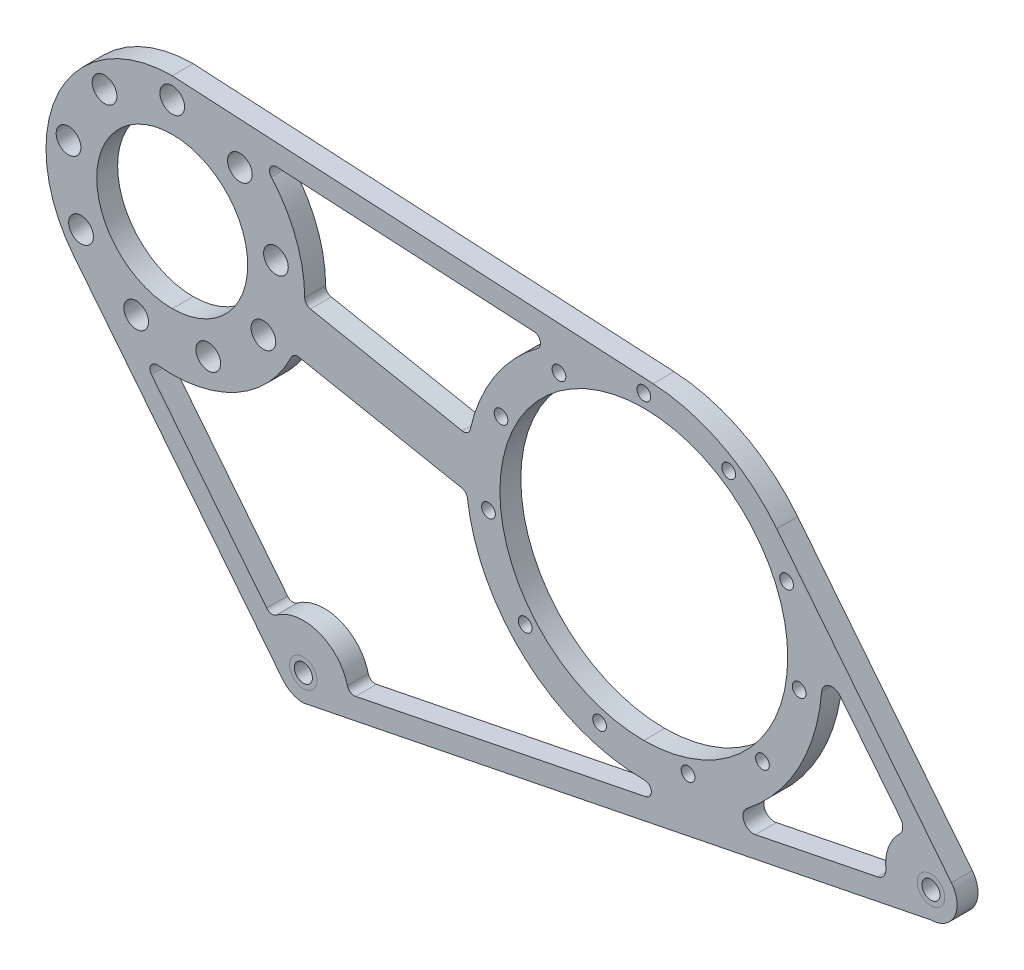
SolidWorks part; units mm, degrees
material "6061-T6 (SS)"
ref_plane "Front Plane" through (0, 0, 0) normal (0, 0, 1) x (1, 0, 0)
ref_plane "Top Plane" through (0, 0, 0) normal (0, 1, 0) x (1, 0, 0)
ref_plane "Right Plane" through (0, 0, 0) normal (1, 0, 0) x (0, 0, -1)
sketch "Sketch1" plane through (0, 0, 0) normal (0, 0, 1) x (1, 0, 0)
  line L0 (0, 0) -> (171.7726, -25.4) construction
  line L1 (47.761, -127.9853) -> (276.361, -82.1437)
  line L2 (0, 45.974) -> (175.1446, 36.4206)
  line L3 (-35.96, -28.6441) -> (40.3107, -124.3949)
  line L4 (220.1994, 13.1746) -> (283.8113, -66.6841)
  line L5 (171.7726, 36.5125) -> (171.7726, 27.0256) construction
  line L6 (0, 27.4955) -> (0, 45.974) construction
  circle A0 centre (0, 0) radius 45.974
  circle A1 centre (171.7726, -25.4) radius 61.9125
  circle A2 centre (171.7726, -25.4) radius 52.4256
  circle A3 centre (0, 0) radius 27.4955
  circle A4 centre (47.761, -118.4603) radius 9.525
  circle A5 centre (276.361, -72.6187) radius 9.525
  circle A6 centre (47.761, -118.4603) radius 3.2995
  circle A7 centre (276.361, -72.6187) radius 3.2995
  circle A19 centre (171.7726, -25.4) radius 57.1691 construction
  circle A21 centre (0, 0) radius 38.354 construction
  point P23 (0, 38.354)
  point P44 (0, 0)
  point P47 (171.7726, 31.7691)
  dimension "D1" = 91.948
  dimension "D2" = 123.825
  dimension "D5" = 104.8512
  dimension "D6" = 54.991
  dimension "D7" = 6.5989
  dimension "D8" = 6.5989
  dimension "D9" = 228.6
  dimension "D10" = 19.05
  dimension "D11" = 19.05
  dimension "D14" = 7.62
  dimension "D3" = 171.7726
  dimension "D4" = 25.4
  dimension "D12" = 117.2
  dimension "D13" = 76.2
extrude "Boss-Extrude1" add sketch "Sketch1" along normal blind 7.62 contours A5 L4 A1 L2 A0 L3 A4 L1 | L2 A0 A3 | A4 L1 A6 | A5 A7 | A1 A2 region at (43.7428, -126.7982, 0) region at (104.2025, -48.9688, 0) region at (268.0231, -68.6005, 0) region at (-40.2441, 19.3945, 0) region at (228.5635, -5.5459, 0)
sketch "Sketch2" plane through (0, 0, 7.62) normal (0, 0, 1) x (1, 0, 0)
  line L0 (171.7726, 36.5125) -> (171.7726, 27.0256) construction
  circle A0 centre (0, 38.354) radius 4.4996
  circle A1 centre (171.7726, 31.7691) radius 2.5006
  circle A2 centre (24.6535, 29.3809) radius 4.4996
  circle A3 centre (37.7713, 6.6601) radius 4.4996
  circle A4 centre (33.2155, -19.177) radius 4.4996
  circle A5 centre (13.1178, -36.041) radius 4.4996
  circle A6 centre (-13.1178, -36.041) radius 4.4996
  circle A7 centre (-33.2155, -19.177) radius 4.4996
  circle A8 centre (-37.7713, 6.6601) radius 4.4996
  circle A9 centre (-24.6535, 29.3809) radius 4.4996
  circle A10 centre (0, 0) radius 38.354 construction
  circle A11 centre (202.6805, 22.6937) radius 2.5006
  circle A12 centre (223.7754, -1.6511) radius 2.5006
  circle A13 centre (228.3597, -33.536) radius 2.5006
  circle A14 centre (214.9781, -62.8378) radius 2.5006
  circle A15 centre (187.879, -80.2533) radius 2.5006
  circle A16 centre (155.6662, -80.2533) radius 2.5006
  circle A17 centre (128.5671, -62.8378) radius 2.5006
  circle A18 centre (115.1854, -33.536) radius 2.5006
  circle A19 centre (119.7698, -1.6511) radius 2.5006
  circle A20 centre (140.8647, 22.6937) radius 2.5006
  circle A21 centre (171.7726, -25.4) radius 57.169 construction
  point P26 (0, 0)
  point P48 (171.7726, -25.4)
  dimension "D1" = 8.9992
  dimension "D2" = 5.0013
  dimension "D3" = 9
extrude "Cut-Extrude1" cut sketch "Sketch2" against normal through all both and the other way through all
ref_plane "Plane1" through (2.54, 0, 0) normal (1, 0, 0) x (0, 0, -1)
ref_plane "Plane2" through (171.7726, 0, 0) normal (1, 0, 0) x (0, 0, -1)
split line "Split Line5"
sketch "Sketch1<4>" plane through (0, 0, 0) normal (0, 0, 1) x (1, 0, 0) same geometry as "Sketch1"
sketch "Sketch4" plane through (0, 0, 7.62) normal (0, 0, 1) x (1, 0, 0)
  circle A0 centre (276.361, -72.6187) radius 3.2995
  circle A1 centre (276.361, -72.6187) radius 5
  circle A2 centre (47.761, -118.4603) radius 3.2995
  circle A3 centre (47.761, -118.4603) radius 5
  dimension "D1" = 10
  dimension "D2" = 6.5989
split line "Split Line6"
split line "Split Line7"
split line "Split Line8"
sketch "Sketch5" plane through (0, 0, 0) normal (0, 0, -1) x (-1, 0, 0)
  line L1 (-265.2464, -55.6078) -> (-243.3096, -28.0683)
  line L2 (-256.8814, -78.2783) -> (-212.4332, -87.1916)
  line L3 (-131.755, 31.156) -> (-38.1271, 36.263)
  line L4 (-105.593, -13.2277) -> (-50.3134, -2.4384)
  line L5 (-172.497, -95.2) -> (-66.7598, -116.4038)
  line L6 (-34.4084, -104.755) -> (7.5527, -52.0767)
  line L7 (-105.4771, -31.3206) -> (-46.1613, -19.7435)
  line L8 (0, 45.974) -> (-175.1446, 36.4206) construction
  line L9 (35.96, -28.6441) -> (-40.3107, -124.3949) construction
  line L10 (-47.761, -127.9853) -> (-276.361, -82.1437) construction
  line L11 (-220.1994, 13.1746) -> (-283.8113, -66.6841) construction
  line L12 (-171.7726, -25.4) -> (-171.7726, 974.6) construction
  arc A0 (-264.9091, -60.7261) -> (-259.9252, -74.1819) centre (-276.361, -72.6187) cw
  arc A1 (-36.0893, 32.0404) -> (-48.26, 0.0519) centre (0, 0) ccw
  arc A2 (-133.1319, 26.5813) -> (-108.5586, -11.2882) centre (-171.7726, -25.4) cw
  arc A3 (-63.7938, -114.5196) -> (-37.9106, -105.2108) centre (-47.761, -118.4603) cw
  arc A4 (-171.9891, -90.1696) -> (-107.5106, -33.496) centre (-171.7726, -25.4) ccw
  arc A5 (5.2877, -47.9695) -> (-43.391, -21.1246) centre (0, 0) cw
  arc A6 (-236.5322, -30.1316) -> (-209.3433, -80.4498) centre (-165.6488, -24.3352) ccw
  arc A7 (-264.9091, -60.7261) -> (-265.2464, -55.6078) centre (-262.2663, -57.9817) cw
  arc A8 (-259.9252, -74.1819) -> (-256.8814, -78.2783) centre (-256.1323, -74.5426) ccw
  arc A9 (-212.4332, -87.1916) -> (-209.3433, -80.4498) centre (-211.684, -83.4559) ccw
  arc A10 (-243.3096, -28.0683) -> (-236.5322, -30.1316) centre (-240.3295, -30.4421) cw
  arc A11 (-37.9106, -105.2108) -> (-34.4084, -104.755) centre (-36.3952, -103.1724) ccw
  arc A12 (-66.7598, -116.4038) -> (-63.7938, -114.5196) centre (-66.2604, -113.9133) ccw
  arc A13 (-172.497, -95.2) -> (-171.9891, -90.1696) centre (-171.9976, -92.7096) cw
  arc A14 (7.5527, -52.0767) -> (5.2877, -47.9695) centre (5.566, -50.4942) ccw
  arc A15 (-43.391, -21.1246) -> (-46.1613, -19.7435) centre (-45.6747, -22.2364) ccw
  arc A16 (-107.5106, -33.496) -> (-105.4771, -31.3206) centre (-104.9905, -33.8135) cw
  arc A17 (-108.5586, -11.2882) -> (-105.593, -13.2277) centre (-106.0796, -10.7347) ccw
  arc A18 (-48.26, 0.0519) -> (-50.3134, -2.4384) centre (-50.8, 0.0546) cw
  arc A19 (-38.1271, 36.263) -> (-36.0893, 32.0404) centre (-37.9887, 33.7268) cw
  arc A20 (-131.755, 31.156) -> (-133.1319, 26.5813) centre (-131.6166, 28.6198) ccw
  point P41 (-267.6332, -58.6042)
  point P44 (-260.5992, -77.5327)
  point P47 (-185.8867, -92.515)
  point P50 (-236.6152, -19.6641)
  point P80 (-44.2058, -19.3618)
  point P83 (-107.3075, -31.6778)
  dimension "D1" = 16.51
  dimension "D6" = 71.12
  dimension "D7" = 3.81
  dimension "D8" = 16.51
  dimension "D11" = 64.77
  dimension "D13" = 64.77
  dimension "D14" = 48.26
  dimension "D15" = 2.54
  dimension "D16" = 48.26
  dimension "D17" = 17.78
  dimension "D2" = 49.784
  dimension "D3" = 76.2
  dimension "D4" = 7.62
  dimension "D5" = 7.62
  dimension "D9" = 7.62
  dimension "D10" = 7.62
  dimension "D12" = 7.62
extrude "Cut-Extrude2" cut sketch "Sketch5" against normal through all both and the other way through all
